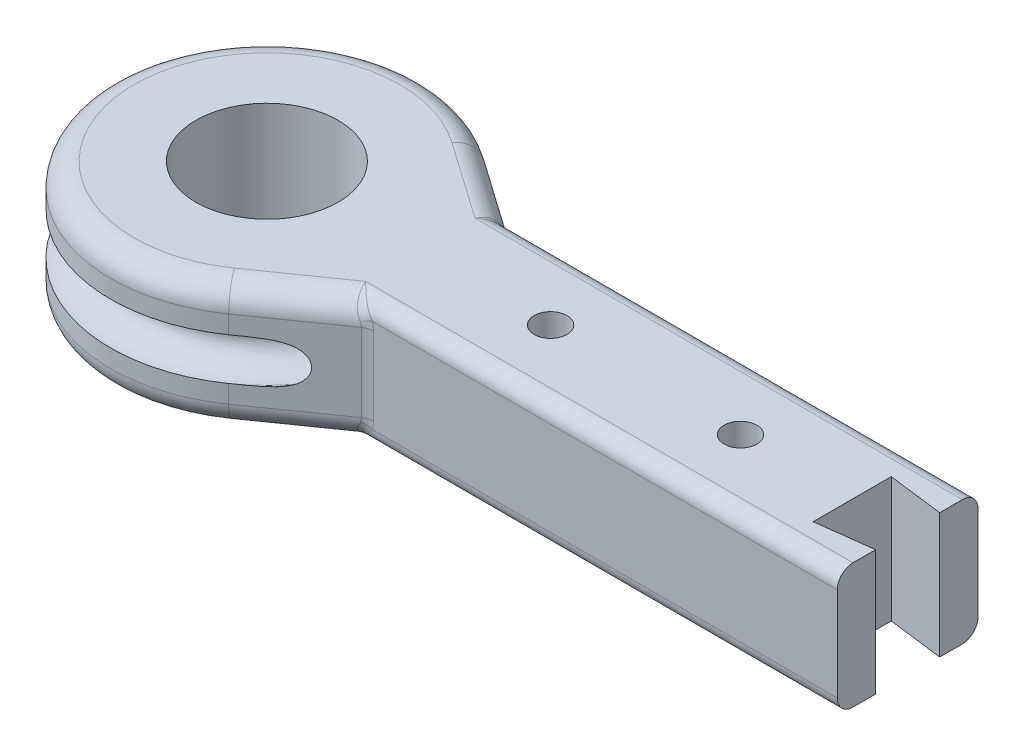
SolidWorks part; units mm, degrees
ref_plane "Front Plane" through (0, 0, 0) normal (0, 0, 1) x (1, 0, 0)
ref_plane "Top Plane" through (0, 0, 0) normal (0, 1, 0) x (1, 0, 0)
ref_plane "Right Plane" through (0, 0, 0) normal (1, 0, 0) x (0, 0, -1)
sketch "Sketch1" plane through (0, 0, 0) normal (0, 1, 0) x (1, 0, 0)
  line L0 (-12.4221, 0) -> (37.45, 0) construction
  line L1 (0, 8.1775) -> (0, -7.8417) construction
  line L2 (11, 4.5) -> (5.7415, 8.1875)
  line L3 (11, -4.5) -> (41, -4.5)
  line L5 (11, 4.5) -> (41, 4.5)
  line L6 (41, -4.5) -> (41, -2.05)
  line L7 (11, -4.5) -> (41, 4.5) construction
  line L8 (11, 4.5) -> (41, -4.5) construction
  line L9 (11, -4.5) -> (5.7415, -8.1875)
  line L10 (11, 4.5) -> (11, -4.5) construction
  line L21 (41, 2.05) -> (37.45, 2.5)
  line L23 (37.45, -2.5) -> (37.45, 2.5)
  line L26 (37.45, -2.5) -> (32.3551, -1.9065) construction
  line L27 (37.45, 2.5) -> (33.2137, 2.1641) construction
  line L28 (41, -2.05) -> (37.45, -2.5)
  line L30 (41, 2.05) -> (41, 4.5)
  arc A0 (5.7415, 8.1875) -> (5.7415, -8.1875) centre (0, 0) ccw
  circle A1 centre (0, 0) radius 4.55
  point P1 (0, 0)
  point P7 (26, 0)
  point P12 (-10, 0)
  point P20 (-4.55, 0)
  point P44 (41, 2.05)
  point P48 (41, -2.05)
  dimension "D1" = 20
  dimension "D4" = 9.1
  dimension "D9" = 3.55
  dimension "D2" = 30
  dimension "D3" = 9
  dimension "D5" = 21
  dimension "D6" = 2
  dimension "D10" = 2
  dimension "D14" = 2.45
extrude "Boss-Extrude2" add sketch "Sketch1" along normal blind 8 contours A1 | L3 L6 L28 L23 L21 L30 L5 L2 A0 L9 region at (0, 0, 0)
sketch "Sketch4" plane through (-6.6668, 16.5353, 0) normal (0, 0, 1) x (0, 1, 0)
  line L2 (-8.5353, -12.4083) -> (-8.5353, 3.3332) construction
  line L3 (-8.5353, 3.3332) -> (-16.5353, 3.3332) construction
  line L8 (-16.5353, -6.6668) -> (-4.9826, -6.6668) construction
  ellipse E0 centre (-12.5353, 3.3332) end of major axis (-11.1853, 3.3332) minor radius 0.7 (-11.1853, 3.3332) -> (-13.8853, 3.3332) ccw
  ellipse E1 centre (-12.5353, 3.3332) end of major axis (-12.5353, 5.1332) minor radius 1.35 (-13.8853, 3.3332) -> (-11.1853, 3.3332) ccw
  point P0 (-12.5353, 3.3332)
  point P1 (-12.5353, 3.3332)
  point P13 (-8.5353, 3.3019)
  point P22 (-12.5353, 3.3332)
  dimension "D1" = 0.7
  dimension "D2" = 1.8
fillet "Fillet2" radius 1.5 6 edges at (8.3707, 0, -6.3438) (8.3707, 0, 6.3438) (8.3707, 8, -6.3438) (8.3707, 8, 6.3438) (-10, 0, 0) (-10, 8, 0)
sketch "Sketch5" plane through (0, 8, 0) normal (0, 1, 0) x (1, 0, 0)
  line L0 (11, 6.5426) -> (11, -6.3371) construction
  line L1 (37.45, 7.6045) -> (37.45, -7.4675) construction
  line L2 (0, 0) -> (39.1502, 0) construction
  circle A0 centre (18.15, 0) radius 1.05
  circle A1 centre (30.3, 0) radius 1.05
  point P0 (11, -4.5)
  point P1 (11, 4.5)
  point P16 (37.45, 0.0685)
  dimension "D2" = 2.1
  dimension "D1" = 7.15
  dimension "D3" = 7.15
extrude "Cut-Extrude1" cut sketch "Sketch5" against normal blind 10 contours A1 | A0
revolve "Cut-Revolve1" cut sketch "Sketch4" angle 360 about L8
fillet "Fillet3" radius 1 4 edges at (24.6937, 0, -4.5) (24.6937, 0, 4.5) (24.6937, 8, -4.5) (24.6937, 8, 4.5)
fillet "Fillet4" radius 1 5 edges at (10.3282, 7.7361, 4.1769) (10.9624, 6.7537, 4.5) (10.3282, 0.2639, 4.1769) (10.9624, 1.2463, 4.5) (11, 4, 4.5)
fillet "Fillet5" radius 1 5 edges at (10.3282, 0.2639, -4.1769) (10.3282, 7.7361, -4.1769) (10.9624, 1.2463, -4.5) (11, 4, -4.5) (10.9624, 6.7537, -4.5)
